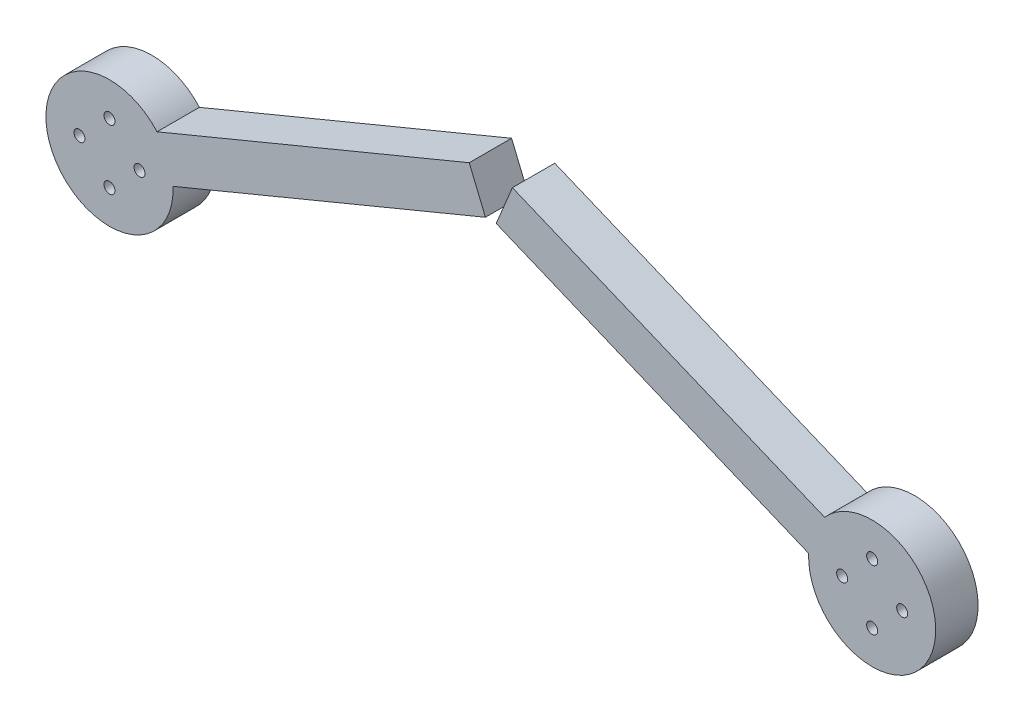
SolidWorks part; units mm, degrees
ref_plane "Front Plane" through (0, 0, 0) normal (0, 0, 1) x (1, 0, 0)
ref_plane "Top Plane" through (0, 0, 0) normal (0, 1, 0) x (1, 0, 0)
ref_plane "Right Plane" through (0, 0, 0) normal (1, 0, 0) x (0, 0, -1)
sketch "Sketch1" plane through (0, 0, 0) normal (0, 0, 1) x (1, 0, 0)
  line L0 (-216.0578, -96.9368) -> (-12.9419, -12.8035)
  line L1 (-216.0578, -96.9368) -> (-206.3377, -120.4034)
  line L2 (-12.9419, -12.8035) -> (-3.2218, -36.27)
  line L3 (-206.3377, -120.4034) -> (-3.2218, -36.27)
  line L4 (12.9419, -12.8035) -> (216.0578, -96.9368)
  line L5 (12.9419, -12.8035) -> (3.2218, -36.27)
  line L6 (216.0578, -96.9368) -> (206.3377, -120.4034)
  line L7 (3.2218, -36.27) -> (206.3377, -120.4034)
  line L8 (-12.9419, -12.8035) -> (0, -7.4427)
  line L9 (0, -7.4427) -> (12.9419, -12.8035)
  line L10 (0, 19.4566) -> (0, -8.1997) construction
  line L11 (-228.6, -115.5981) -> (-228.6, -77.4981) construction
  line L12 (228.6, -115.5981) -> (228.6, -77.4981) construction
  circle A0 centre (-228.6, -115.5981) radius 38.1
  circle A3 centre (-228.6, -115.5981) radius 85.471 construction
  circle A4 centre (228.6, -115.5981) radius 38.1
  circle A5 centre (228.6, -115.5981) radius 85.471 construction
  point P7 (0, 0)
  point P13 (206.3377, -120.4034)
  point P16 (-228.6, -97.5981)
  point P17 (228.6, -97.5981)
  point P21 (-166.8982, -77.6365)
  point P22 (195.3269, -112.715)
  point P24 (238.0524, -152.1181)
  point P27 (0, 0)
  point P28 (-228.6, -115.5981)
  point P29 (-222.7721, -49.2855)
  dimension "D5" = 76.2
  dimension "D6" = 170.942
  dimension "D1" = 135
  dimension "D2" = 25.4
  dimension "D3" = 25.4
  dimension "D4" = 18
  dimension "D7" = 18
  dimension "D8" = 457.2
extrude "Boss-Extrude1" add sketch "Sketch1" along normal blind 25.4 contours L0 A0 L3 L1 | L3 A0 L0 L1 | A0 L3 L2 L0 | A4 L4 L5 L7 | L4 A4 L7 L6 | L7 A4 L4 L6 region at (-231.6167, -116.8177, 0) region at (-202.5788, -105.078, 0) region at (101.0237, -63.0366, 0) region at (-101.0237, -63.0366, 0) region at (231.6167, -116.8177, 0) region at (202.5788, -105.078, 0)
hole_wizard "M6 Clearance Hole1" positions "3DSketch2" profile "Sketch3" hole size "M6" standard "ANSI Metric" end condition through all
sketch3d "3DSketch2"
  point P2 (-228.6, -97.5981, 0)
  point P10 (0, 0, 0)
sketch "Sketch3" plane through (-228.6, -97.5981, 0) normal (1, 0, 0) x (0, 1, 0)
  line L0 (0, 0) -> (0, 25.4)
  line L1 (0, 25.4) -> (3.3, 25.4)
  line L2 (3.3, 25.4) -> (3.3, 0)
  line L5 (3.3, 0) -> (0, 0)
  line L11 (0, -6.35) -> (0, 107.95) construction
  dimension "Thru Hole Dia." = 6.6
  dimension "Thru Hole Depth" = 25.4
pattern_circular "CirPattern1" count 4 over 360 about axis through (-228.6, -115.5981, 25.4) along (0, 0, -1) of "M6 Clearance Hole1"
mirror "Mirror3" about plane through (0, 0, 0) normal (1, 0, 0) of "CirPattern1"
equation "\"Rover_Length\"= 25in"
equation "\"Rover_Width\"= 18in"
equation "\"Rover_Height\"= 12in"
equation "\"Chassis_Wheelbase\"= 18in"
equation "\"Chassis_WheelDiam\" = 171mm"
equation "\"Chassis_ArmDiamWidth\"= 0.75in"
equation "\"Chassis_ArmAngle\"= 135deg"
equation "\"Chassis_HubMountOD\"= 3in"
equation "\"Chassis_WheelBoltHole\"= 36mm"
equation "\"Chassis_WheelBoltNum\"= 4"
equation "\"Chassis_DiffBarLength\"= 12in"
equation "\"Chassis_DiffBarWidth\"= 1in"
equation "\"Chassis_DiffBarHeight\"= 0.5in"
equation "\"Chassis_DiffLinkage_Length\"= 2.5in"
equation "\"D1@Sketch1\"=\"Chassis_ArmAngle\""
equation "\"D2@Sketch1\"=\"Chassis_DiffBarWidth\""
equation "\"D3@Sketch1\"=\"Chassis_DiffBarWidth\""
equation "\"D5@Sketch1\"=\"Chassis_HubMountOD\""
equation "\"D4@Sketch1\"=\"Chassis_WheelBoltHole\"/2"
equation "\"D7@Sketch1\"=\"Chassis_WheelBoltHole\"/2"
equation "\"D8@Sketch1\"=\"Chassis_Wheelbase\""
equation "\"D1@Boss-Extrude1\"=\"Chassis_DiffBarWidth\""
